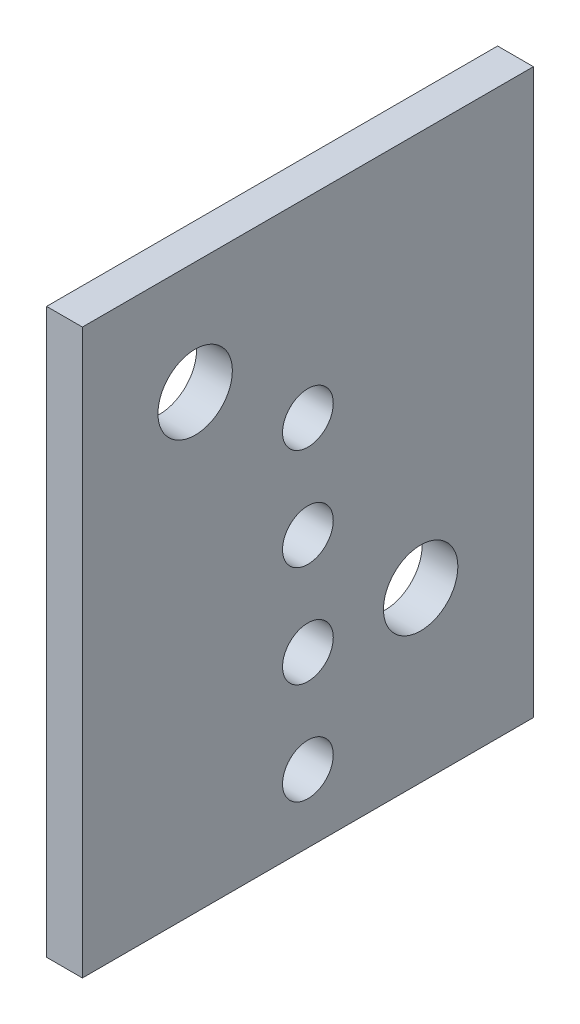
SolidWorks part; units mm, degrees
ref_plane "Front Plane" through (0, 0, 0) normal (0, 0, 1) x (1, 0, 0)
ref_plane "Top Plane" through (0, 0, 0) normal (0, 1, 0) x (1, 0, 0)
ref_plane "Right Plane" through (0, 0, 0) normal (1, 0, 0) x (0, 0, -1)
sketch "Sketch1" plane through (0, 0, 0) normal (1, 0, 0) x (0, 0, -1)
  line L1 (0, 0) -> (40, 0)
  line L2 (0, 0) -> (0, -50)
  line L3 (0, -50) -> (40, -50)
  line L4 (40, 0) -> (40, -50)
  circle A0 centre (30, -35.04) radius 3.3
  circle A1 centre (10, -10) radius 3.3
  circle A2 centre (20, -16.9748) radius 2.25
  circle A3 centre (20, -25.9748) radius 2.25
  circle A4 centre (20, -34.9748) radius 2.25
  circle A5 centre (20, -43.9748) radius 2.25
  point P17 (0, 0)
  point P18 (0, 0)
  point P19 (0, 0)
  dimension "D3" = 6.6
  dimension "D4" = 6.6
  dimension "D9" = 4.5
  dimension "D10" = 4.5
  dimension "D11" = 4.5
  dimension "D14" = 4.5
  dimension "D1" = 50
  dimension "D2" = 40
  dimension "D5" = 10
  dimension "D6" = 14.96
  dimension "D7" = 10
  dimension "D8" = 10
  dimension "D12" = 9
  dimension "D13" = 9
  dimension "D15" = 9
  dimension "D16" = 20
extrude "Boss-Extrude1" add sketch "Sketch1" along normal blind 3.175
